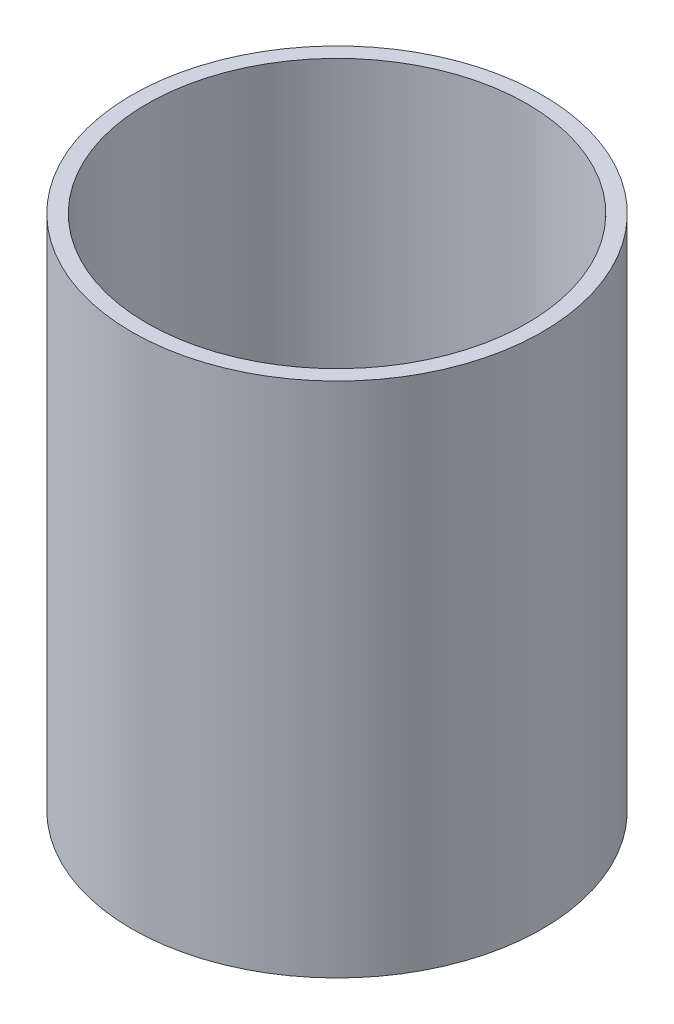
SolidWorks part; units mm, degrees
material "Corrugated Paper"
ref_plane "Front Plane" through (0, 0, 0) normal (0, 0, 1) x (1, 0, 0)
ref_plane "Top Plane" through (0, 0, 0) normal (0, 1, 0) x (1, 0, 0)
ref_plane "Right Plane" through (0, 0, 0) normal (1, 0, 0) x (0, 0, -1)
ref_axis "Axis1" through (0, 55, 0) along (0, -1, 0)
sketch "Sketch1" plane through (0, 0, 0) normal (0, 0, 1) x (1, 0, 0)
  line L1 (-42.8625, 36.9791) -> (-39.6875, 36.9791)
  line L2 (-42.8625, 36.9791) -> (-42.8625, -70.9709)
  line L3 (-42.8625, -70.9709) -> (-39.6875, -70.9709)
  line L4 (-39.6875, 36.9791) -> (-39.6875, -70.9709)
  line L5 (0, 36.9791) -> (-38.1, 36.9791) construction
  line L6 (0, -70.9709) -> (-38.1, -70.9709) construction
  dimension "D1" = 3.175
revolve "Revolve1" add sketch "Sketch1" angle 360 about axis through (0, 55, 0) along (0, -1, 0)
